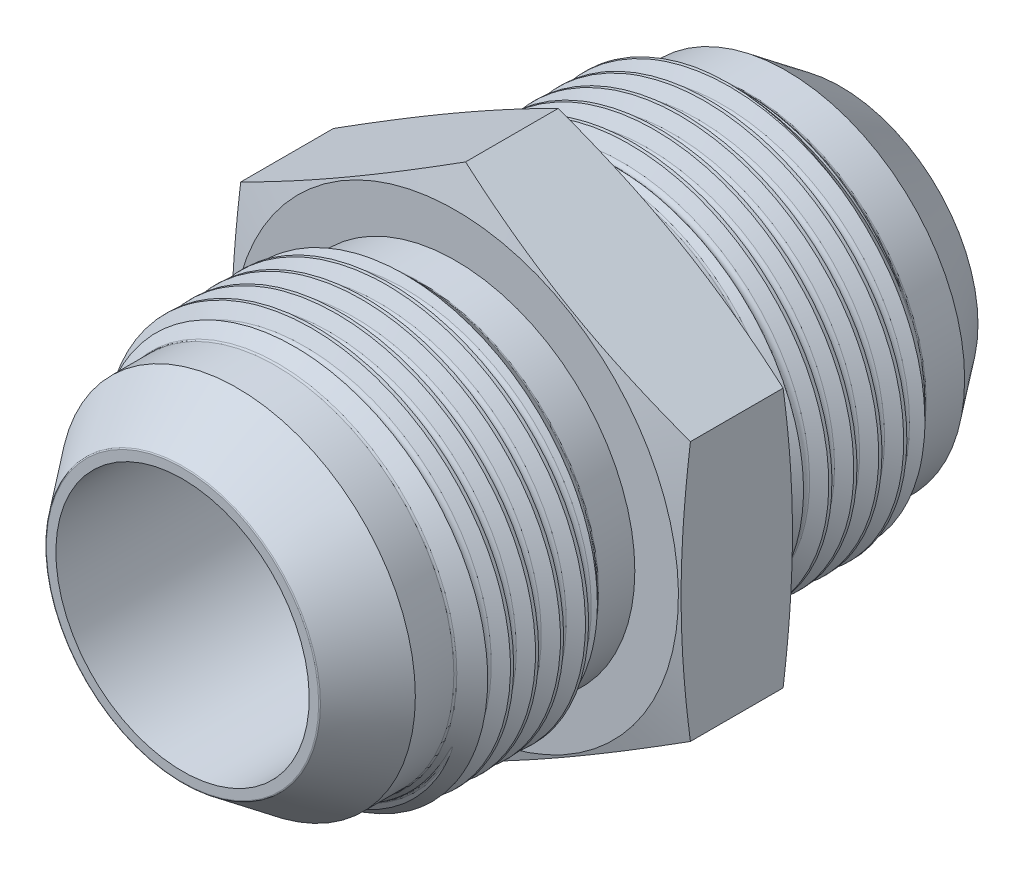
SolidWorks part; units mm, degrees
ref_plane "Front Plane" through (0, 0, 0) normal (0, 0, 1) x (1, 0, 0)
ref_plane "Top Plane" through (0, 0, 0) normal (0, 1, 0) x (1, 0, 0)
ref_plane "Right Plane" through (0, 0, 0) normal (1, 0, 0) x (0, 0, -1)
sketch "Sketch0" plane through (0, 0, 0) normal (1, 0, 0) x (0, 0, -1)
  line L0 (-27.9019, 0) -> (0, 0) construction
  line L1 (0, 0) -> (27.9019, 0) construction
  line L2 (-19.9009, 16.6687) -> (-19.9009, -16.6687) construction
  line L3 (-27.9019, 10.7315) -> (-27.9019, -10.7315) construction
  line L4 (-27.9019, 11.5951) -> (-27.9019, -11.5951) construction
  line L5 (-23.2672, 15.0876) -> (-23.2672, -15.0876) construction
  line L6 (-27.9019, 11.5951) -> (-23.2672, 15.0876) construction
  line L7 (-23.2672, 15.0876) -> (-19.9009, 15.0876) construction
  line L8 (-19.9009, 15.0876) -> (-19.9009, -15.0876) construction
  line L9 (-4.7625, 19.05) -> (-4.7625, -19.05) construction
  line L10 (-4.7625, 18.8722) -> (-4.7625, -18.8722) construction
  line L11 (-19.9009, 15.0876) -> (-19.9009, 16.6687) construction
  line L12 (-19.9009, 16.6687) -> (-7.9375, 16.6687) construction
  line L13 (-7.9375, 16.6687) -> (-7.9375, 15.1765) construction
  line L14 (-7.9375, 15.1765) -> (-4.7625, 15.1765) construction
  line L15 (-7.9375, 15.1765) -> (-7.9375, -15.1765) construction
  line L16 (-4.7625, 0) -> (-4.9657, 0) construction
  point P8 (-4.7625, 0)
  point P13 (-23.2672, 0)
  point P14 (-19.9009, 0)
  point P24 (-7.9375, 0)
  point P26 (-4.7625, 0)
  point P27 (4.7625, 0)
  dimension "37" = 37
sketch "Sketch1" plane through (0, 0, 0) normal (1, 0, 0) x (0, 0, -1)
  line L0 (-27.9019, 0) -> (0, 0)
  line L1 (-27.9019, 0) -> (-27.9019, 11.5318)
  line L2 (-27.8513, 11.6332) -> (-23.2672, 15.0876)
  line L3 (-23.2672, 15.0876) -> (-20.0061, 15.0876)
  line L4 (-19.8265, 15.162) -> (-18.3198, 16.6687)
  line L5 (-18.3198, 16.6687) -> (-9.4298, 16.6688)
  line L6 (-9.4298, 16.6688) -> (-8.0119, 15.2509)
  line L7 (-7.8323, 15.1765) -> (0, 15.1765)
  line L8 (0, 15.1765) -> (0, 0)
  line L10 (-19.9009, 16.6687) -> (-19.9009, -16.6687) construction
  line L11 (-19.812, 0) -> (0, 0) construction
  line L12 (-27.9019, 10.7315) -> (-27.9019, -10.7315) construction
  line L13 (-19.9009, 16.6687) -> (-7.9375, 16.6687) construction
  line L15 (-7.9375, 16.6687) -> (-7.9375, 15.1765) construction
  arc A0 (-27.9019, 11.5318) -> (-27.8513, 11.6332) centre (-27.7749, 11.5318) cw
  arc A1 (-20.0061, 15.0876) -> (-19.8265, 15.162) centre (-20.0061, 15.3416) ccw
  arc A2 (-8.0119, 15.2509) -> (-7.8323, 15.1765) centre (-7.8323, 15.4305) ccw
  point P27 (-27.9019, 11.5951)
  point P30 (-19.9009, 15.0876)
  point P33 (-7.9375, 15.1765)
  dimension "D1" = 0.127
  dimension "D2" = 0.254
  dimension "D3" = 45
  dimension "D4" = 45
revolve "Revolve1" add sketch "Sketch1" angle 360 about L11
sketch "Sketch2" plane through (0, 0, 27.9019) normal (0, 0, 1) x (1, 0, 0)
  circle A0 centre (0, 0) radius 16.6687
  point P3 (0, 16.6687)
curve "Helix/Spiral1" pitch 2.1167 height 25.2561 turns 11.932 parameters "Pitch"=2.1167
sketch "Sketch3" plane through (0, 0, 0) normal (1, 0, 0) x (0, 0, -1)
  line L0 (-29.8863, 16.8979) -> (-28.8279, 15.0648) construction
  line L1 (-28.8279, 15.0648) -> (-27.7696, 16.8979) construction
  line L2 (-27.7696, 16.8979) -> (-29.8863, 16.8979) construction
  line L3 (-27.9019, 16.6687) -> (-29.754, 16.6687) construction
  line L4 (-28.8279, 16.8979) -> (-28.8279, 16.6687) construction
  line L5 (-29.0484, 15.4467) -> (-28.6075, 15.4467) construction
  line L6 (-28.8279, 15.4467) -> (-28.8279, 15.0648) construction
  line L7 (-29.8201, 16.7833) -> (-29.1587, 15.6376)
  line L8 (-29.8201, 16.7833) -> (-27.8358, 16.7833)
  line L9 (-27.8358, 16.7833) -> (-28.4972, 15.6376)
  line L10 (-28.8279, 15.0648) -> (-28.8279, -16.6687) construction
  line L11 (-28.8279, -16.6687) -> (-26.7113, -16.6687) construction
  line L12 (-26.7113, -16.6687) -> (-24.5946, -16.6687) construction
  line L13 (-24.5946, -16.6687) -> (-22.4779, -16.6688) construction
  line L14 (-22.4779, -16.6688) -> (-20.3613, -16.6687) construction
  line L15 (-20.3613, -16.6687) -> (-18.2446, -16.6687) construction
  line L16 (-18.2446, -16.6687) -> (-16.1279, -16.6687) construction
  line L17 (-16.1279, -16.6687) -> (-14.0113, -16.6687) construction
  line L21 (-18.3198, -16.6687) -> (-9.4298, -16.6687) construction
  arc A0 (-29.1587, 15.6376) -> (-28.4972, 15.6376) centre (-28.8279, 15.8286) ccw
  point P13 (-28.8279, 16.7833)
sweep "Cut-Sweep1" cut profiles "Sketch3" path "Helix/Spiral1" align with end faces yes
ref_axis "Axis1" through (-10.4775, 0, 0) along (1, 0, 0)
pattern_circular "CirPattern1" count 2 over 180 about axis through (-10.4775, 0, 0) along (1, 0, 0) reverse direction yes of bodies 103
sketch "Sketch4" plane through (0, 0, 0) normal (0, 0, 1) x (1, 0, 0)
  line L1 (0, 21.997) -> (-19.05, 10.9985)
  line L2 (-19.05, 10.9985) -> (-19.05, -10.9985)
  line L3 (-19.05, -10.9985) -> (0, -21.997)
  line L4 (0, -21.997) -> (19.05, -10.9985)
  line L5 (19.05, -10.9985) -> (19.05, 10.9985)
  line L6 (19.05, 10.9985) -> (0, 21.997)
  circle A0 centre (0, 0) radius 19.05 construction
extrude "Boss-Extrude1" add sketch "Sketch4" along normal up to vertex (4.7625 mm away) and the other way up to vertex (4.7625 mm away) up to point (0, 0, 4.7625) other way up to point (0, 0, -4.7625)
sketch "Sketch5" plane through (0, 0, 0) normal (1, 0, 0) x (0, 0, -1)
  line L0 (-4.7625, 25.1219) -> (4.7625, 25.1219)
  line L1 (-4.7625, 25.1219) -> (-4.7625, 18.8722)
  line L2 (-4.7625, 18.8722) -> (-3.9252, 21.997)
  line L3 (-3.9252, 21.997) -> (3.9252, 21.997)
  line L4 (3.9252, 21.997) -> (4.7625, 18.8722)
  line L5 (4.7625, 18.8722) -> (4.7625, 25.1219)
  line L7 (-4.7625, 21.997) -> (4.7625, 21.997) construction
  line L8 (-4.7625, 0) -> (0, 0) construction
  dimension "D1" = 15
revolve "Cut-Revolve1" cut sketch "Sketch5" angle 360 about L8
sketch "Sketch6" plane through (0, 0, 0) normal (1, 0, 0) x (0, 0, -1)
  line L0 (-27.9019, 10.7315) -> (0, 10.7315)
  line L1 (10.7315, 0) -> (-27.9019, 0)
  line L2 (-27.9019, 0) -> (-27.9019, 10.7315)
  arc A0 (0, 10.7315) -> (10.7315, 0) centre (0, 0) cw
revolve "Cut-Revolve2" cut sketch "Sketch6" angle 360 about L1
pattern_circular "CirPattern2" count 2 over 180 about axis through (-10.4775, 0, 0) along (1, 0, 0) of "Cut-Revolve2" reverse direction yes
equation "\"D3@Helix/Spiral1\" = \"Pitch@Helix/Spiral1\" + \"J@Sketch0\""
equation "\"P@Sketch3\" = \"Pitch@Helix/Spiral1\""
equation "\"H/8@Sketch3\" = \"H@Sketch3\" / 8"
equation "\"2/3H@Sketch3\" = 2/3 * \"H@Sketch3\""
